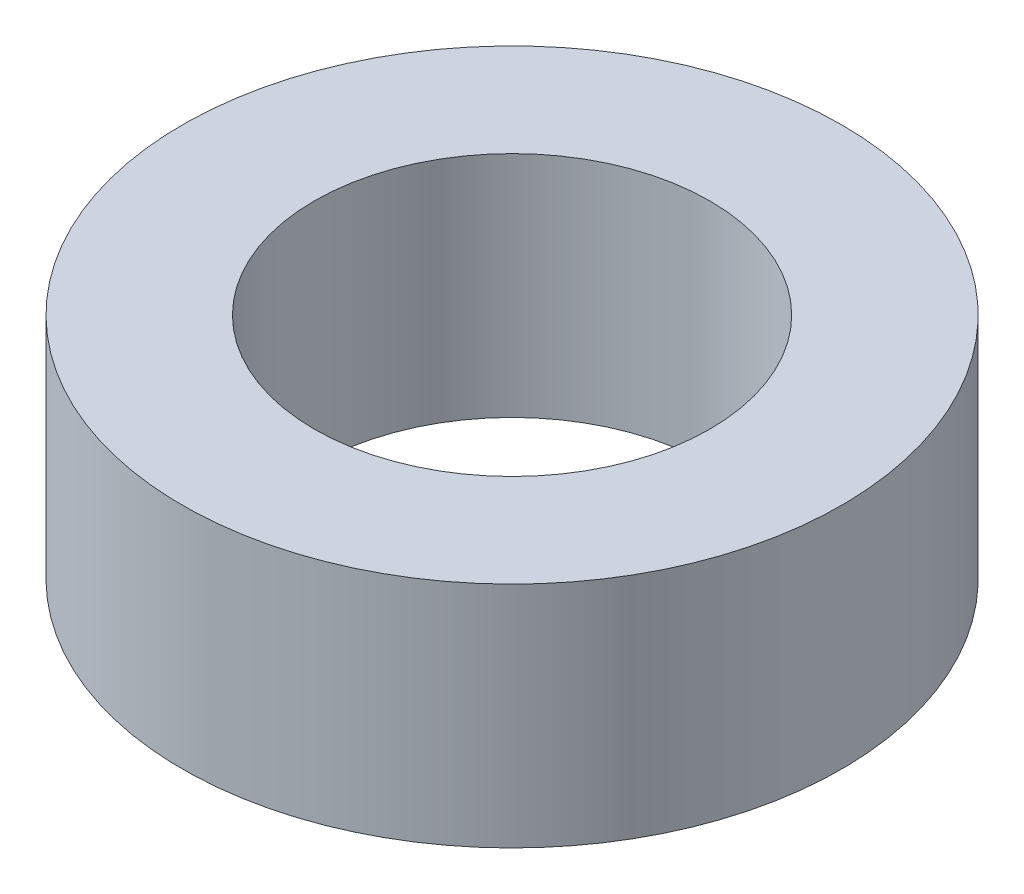
SolidWorks part; units mm, degrees
ref_plane "Front Plane" through (0, 0, 0) normal (0, 0, 1) x (1, 0, 0)
ref_plane "Top Plane" through (0, 0, 0) normal (0, 1, 0) x (1, 0, 0)
ref_plane "Right Plane" through (0, 0, 0) normal (1, 0, 0) x (0, 0, -1)
sketch "Sketch1" plane through (0, 0, 0) normal (0, 1, 0) x (1, 0, 0)
  circle A0 centre (0, 0) radius 37.5
  dimension "FLANGE_OD" = 75
extrude "Boss-Extrude1" add sketch "Sketch1" along normal blind 26
sketch "Sketch2" plane through (0, 0, 0) normal (0, 1, 0) x (1, 0, 0)
  circle A0 centre (0, 0) radius 22.5
  dimension "BORE_D" = 45
extrude "Cut-Extrude1" cut sketch "Sketch2" along normal through all
sketch "Sketch3" plane through (0, 26, 0) normal (0, 1, 0) x (1, 0, 0)
  circle A0 centre (0, 0) radius 13.6605 construction
  circle A1 centre (-13.6605, 0) radius 2.4026
  dimension "BOLT_D" = 4.8051
  dimension "BOLT_PCD" = 27.3211
extrude "Cut-Extrude2" cut sketch "Sketch3" against normal blind 17.4957 rebuild error yes
pattern_circular "CirPattern1" count 3 over 360 rebuild error yes
